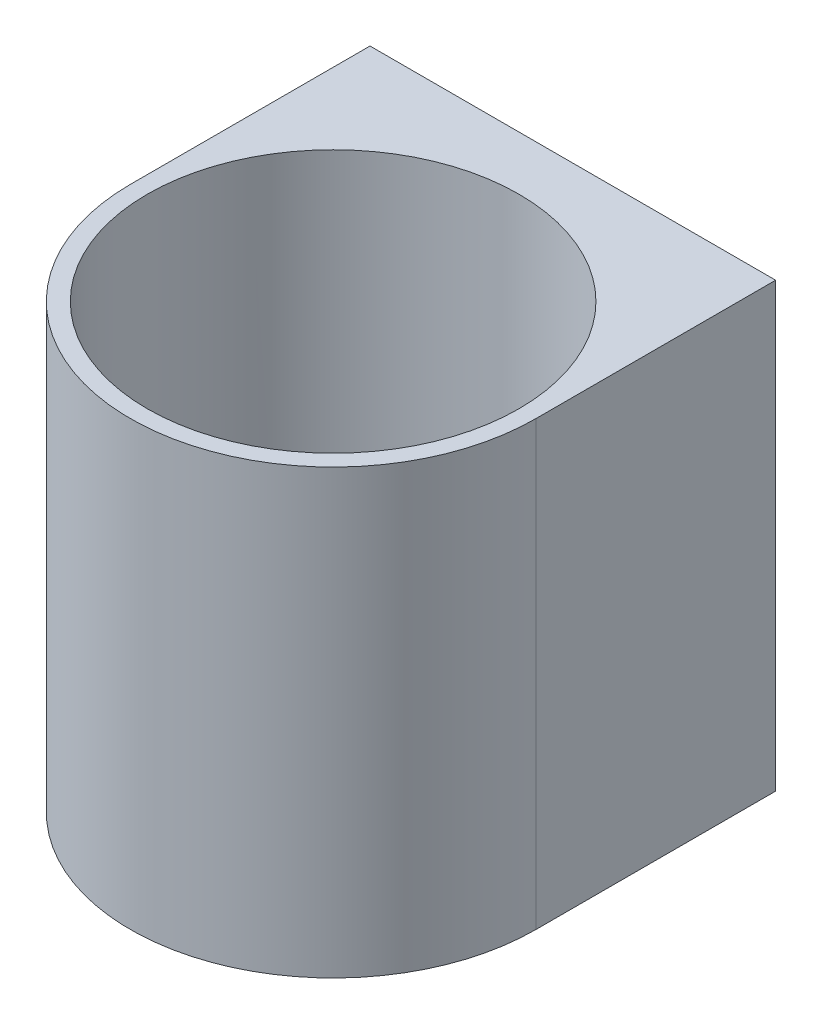
SolidWorks part; units mm, degrees
ref_plane "Front Plane" through (0, 0, 0) normal (0, 0, 1) x (1, 0, 0)
ref_plane "Top Plane" through (0, 0, 0) normal (0, 1, 0) x (1, 0, 0)
ref_plane "Right Plane" through (0, 0, 0) normal (1, 0, 0) x (0, 0, -1)
sketch "Sketch1" plane through (0, 0, 0) normal (0, 1, 0) x (1, 0, 0)
  line L1 (-45.5066, 16.4638) -> (9.4934, 16.4638)
  line L2 (-45.5066, 16.4638) -> (-45.5066, -16.0362)
  line L3 (-45.5066, -16.0362) -> (9.4934, -16.0362)
  line L4 (9.4934, 16.4638) -> (9.4934, -16.0362)
  circle A0 centre (-18.0066, -16.0362) radius 27.5
  circle A1 centre (-18.0066, -16.0362) radius 25.2
  dimension "D1" = 32.5
  dimension "D2" = 55
extrude "Boss-Extrude2" add sketch "Sketch1" along normal blind 60 contours A0 L4 L1 L2 | L3 A1 | L3 A1 | A0 region at (-18.0066, 0, -15.825) region at (-18.0066, 0, 5.341) region at (-18.0066, 0, 26.7314)
sketch "Sketch3" plane through (0, 0, 0) normal (0, -1, 0) x (-1, 0, 0)
  circle A0 centre (18.0066, -16.0362) radius 25.2
extrude "Boss-Extrude3" add sketch "Sketch3" against normal blind 9.3
sketch "Sketch4" plane through (0, 9.3, 0) normal (0, 1, 0) x (1, 0, 0)
  line L0 (-18.0066, -41.2362) -> (-18.0066, 9.1638)
  line L1 (-43.2066, -16.0362) -> (7.1934, -16.0362)
  circle A0 centre (-18.0066, -16.0362) radius 25.2 construction
  circle A1 centre (-18.0066, -16.0362) radius 25.2 construction
  circle A2 centre (-18.0066, -16.0362) radius 1.75
  circle A3 centre (-8.0066, -16.0362) radius 1.75
  circle A4 centre (1.9934, -16.0362) radius 1.75
  circle A5 centre (-18.0066, -6.0362) radius 1.75
  circle A6 centre (-18.0066, 3.9638) radius 1.75
  circle A7 centre (-28.0066, -16.0362) radius 1.75
  circle A8 centre (-38.0066, -16.0362) radius 1.75
  circle A9 centre (-18.0066, -26.0362) radius 1.75
  circle A10 centre (-18.0066, -36.0362) radius 1.75
  circle A11 centre (-28.0066, -6.0362) radius 1.75
  circle A12 centre (-8.0066, -6.0362) radius 1.75
  circle A13 centre (-8.0066, -26.0362) radius 1.75
  circle A14 centre (-28.0066, -26.0362) radius 1.75
  circle A15 centre (-18.0066, -1.0362) radius 1.75
  circle A16 centre (-23.0066, -6.0362) radius 1.75
  circle A17 centre (-13.0066, -6.0362) radius 1.75
  circle A18 centre (-18.0066, -11.0362) radius 1.75
  circle A19 centre (-18.0066, -21.0362) radius 1.75
  circle A20 centre (-18.0066, -31.0362) radius 1.75
  circle A21 centre (-23.0066, -16.0362) radius 1.75
  circle A22 centre (-33.0433, -16.0362) radius 1.75
  circle A23 centre (-13.0066, -16.0362) radius 1.75
  circle A24 centre (-3.1187, -16.0362) radius 1.75
  circle A25 centre (-13.0066, -21.0362) radius 1.75
  circle A26 centre (-23.0066, -21.0362) radius 1.75
  circle A27 centre (-28.0066, -21.0362) radius 1.75
  circle A28 centre (-33.0066, -21.0362) radius 1.75
  circle A29 centre (-23.0066, -26.0362) radius 1.75
  circle A30 centre (-13.0066, -26.0362) radius 1.75
  circle A31 centre (-13.0066, -31.0362) radius 1.75
  circle A32 centre (-23.0066, -31.0362) radius 1.75
  circle A33 centre (-8.0066, -21.0362) radius 1.75
  circle A34 centre (-3.0066, -21.0362) radius 1.75
  circle A35 centre (-23.0066, -11.0362) radius 1.75
  circle A36 centre (-28.0066, -11.0362) radius 1.75
  circle A37 centre (-33.0066, -11.0362) radius 1.75
  circle A38 centre (-13.0066, -11.0362) radius 1.75
  circle A39 centre (-8.0066, -11.0362) radius 1.75
  circle A40 centre (-3.0066, -11.0362) radius 1.75
  circle A41 centre (-23.0066, -1.0362) radius 1.75
  circle A42 centre (-13.0066, -1.0362) radius 1.75
  dimension "D1" = 10
  dimension "D2" = 10
  dimension "D3" = 10
  dimension "D4" = 10
  dimension "D9" = 5
  dimension "D15" = 5
  dimension "D5" = 10
  dimension "D6" = 10
  dimension "D7" = 10
  dimension "D8" = 10
  dimension "D10" = 5
  dimension "D11" = 5
  dimension "D12" = 5
  dimension "D13" = 5
  dimension "D14" = 5
  dimension "D16" = 5
  dimension "D17" = 5
  dimension "D18" = 5
  dimension "D19" = 5
  dimension "D20" = 5
  dimension "D21" = 5
  dimension "D22" = 5
  dimension "D23" = 5
  dimension "D24" = 5
extrude "Cut-Extrude1" cut sketch "Sketch4" against normal through all contours L0 A6 | L0 A6 | L0 A5 | L0 A5 | A11 | A12 | L1 A3 | L1 A3 | L1 A4 | L1 A4 | L0 A2 L1 | L0 A2 L1 | L1 A2 L0 | L1 A2 L0 | L1 A8 | L1 A8 | A14 | L0 A9 | L0 A9 | A13 | L0 A10 | L0 A10 | L1 A7 | L1 A7 | A7 | A37 | A36 | A35 | A16 | A41 | A15 | A42 | A17 | A38 | A39 | A40 | A24 | A34 | A33 | A25 | A23 | A18 | A21 | A22 | A28 | A27 | A26 | A19 | A31 | A20 | A32 | A29 | A30 region at (-18.7493, 9.3, 36.0362) region at (-38.0066, 9.3, 16.7789) region at (-38.0066, 9.3, 15.2935) region at (-28.0066, 9.3, 16.7789) region at (-28.0066, 9.3, 15.2935) region at (-18.7493, 9.3, -3.9638) region at (-17.2639, 9.3, -3.9638) region at (-18.7493, 9.3, 6.0362) region at (-17.2639, 9.3, 6.0362) region at (1.9934, 9.3, 15.2935) region at (1.9934, 9.3, 16.7789) region at (-8.0066, 9.3, 15.2935) region at (-8.0066, 9.3, 16.7789) region at (-18.7493, 9.3, 16.7789) region at (-17.2639, 9.3, 16.7789) region at (-18.7493, 9.3, 26.0362) region at (-17.2639, 9.3, 26.0362) region at (-17.2639, 9.3, 36.0362) region at (-18.7493, 9.3, 15.2935) region at (-17.2639, 9.3, 15.2935) region at (-28.0066, 9.3, 6.0362) region at (-8.0066, 9.3, 6.0362) region at (-8.0066, 9.3, 26.0362) region at (-28.0066, 9.3, 26.0362)
